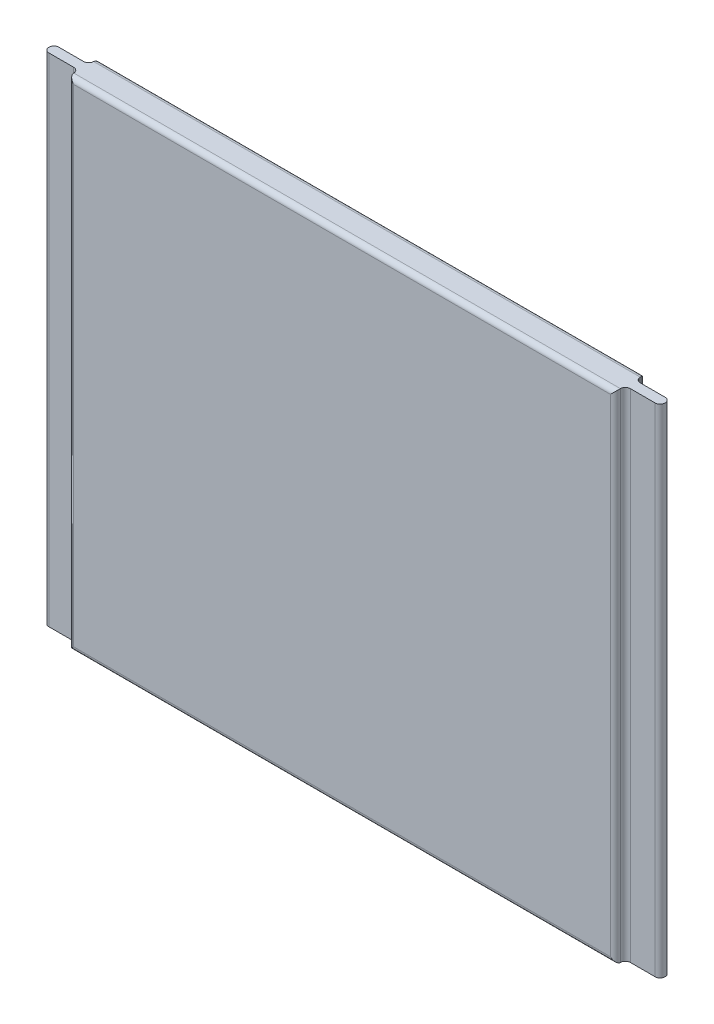
SolidWorks part; units mm, degrees
ref_plane "Front Plane" through (0, 0, 0) normal (0, 0, 1) x (1, 0, 0)
ref_plane "Top Plane" through (0, 0, 0) normal (0, 1, 0) x (1, 0, 0)
ref_plane "Right Plane" through (0, 0, 0) normal (1, 0, 0) x (0, 0, -1)
sketch "Sketch2" plane through (0, 0, 0) normal (0, 1, 0) x (1, 0, 0)
  line L0 (0, 3) -> (0, -3) construction
  line L1 (-55, 3) -> (55, 3)
  line L2 (-55, 3) -> (-55, 2)
  line L3 (-55, -3) -> (55, -3)
  line L4 (55, 3) -> (55, 2)
  line L5 (-55, 3) -> (55, -3) construction
  line L6 (-55, -3) -> (55, 3) construction
  line L7 (-56, 1) -> (-61, 1)
  line L9 (-56, -1) -> (-61, -1)
  line L11 (-55, -2) -> (-55, -3)
  line L12 (56, -1) -> (61, -1)
  line L14 (56, 1) -> (61, 1)
  line L15 (55, -2) -> (55, -3)
  arc A2 (-55, -2) -> (-56, -1) centre (-56, -2) ccw
  arc A3 (-55, 2) -> (-56, 1) centre (-56, 2) cw
  arc A4 (55, -2) -> (56, -1) centre (56, -2) cw
  arc A7 (55, 2) -> (56, 1) centre (56, 2) ccw
  arc A8 (-61, 1) -> (-61, -1) centre (-61, 0) ccw
  arc A9 (61, 1) -> (61, -1) centre (61, 0) cw
  point P0 (0, 0)
  point P9 (-62, 0)
  point P20 (-55, -1)
  dimension "D6" = 2
  dimension "D7" = 62
  dimension "D8" = 1
  dimension "D9" = 1
  dimension "D3" = 0
  dimension "D4" = 0
  dimension "D1" = 110
  dimension "D2" = 2
  dimension "D5" = 2
extrude "Boss-Extrude1" add sketch "Sketch2" along normal blind 100
fillet "Fillet1" radius 1 8 edges at (55, 50, -3) (0, 100, -3) (-55, 50, -3) (0, 0, -3) (-55, 50, 3) (0, 100, 3) (55, 50, 3) (0, 0, 3)
